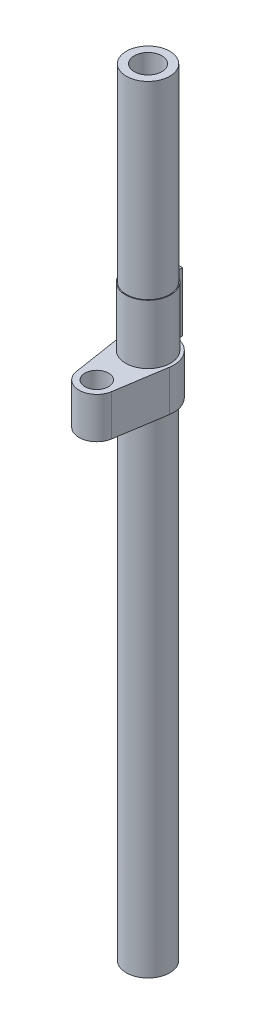
SolidWorks part; units mm, degrees
ref_plane "Ön Düzlem" through (0, 0, 0) normal (0, 0, 1) x (1, 0, 0)
ref_plane "Üst Düzlem" through (0, 0, 0) normal (0, 1, 0) x (1, 0, 0)
ref_plane "Sağ Düzlem" through (0, 0, 0) normal (1, 0, 0) x (0, 0, -1)
sketch "Sketch1" plane through (0, 0, 0) normal (0, 1, 0) x (1, 0, 0)
  circle A0 centre (0, 0) radius 2.75
  dimension "D1" = 5.5
extrude "Boss-Extrude1" add sketch "Sketch1" along normal blind 98.4
sketch "Sketch2" plane through (0, 0, 0) normal (0, -1, 0) x (1, 0, 0)
  circle A0 centre (0, 0) radius 1.75
  dimension "D1" = 3.5
extrude "Cut-Extrude1" cut sketch "Sketch2" against normal blind 10.15
extrude "Cut-Extrude2" cut sketch "Sketch2<2>" along normal blind 10.15 from surface starting at face at (0, 98.4, 2.75)
sketch "Sketch2<2>" plane through (0, 0, 0) normal (0, -1, 0) x (1, 0, 0) same geometry as "Sketch2"
ref_plane "Plane1" through (-2.75, 0, 0) normal (-1, 0, 0) x (0, 0, 1)
sketch "Sketch3" plane through (-2.75, 0, 0) normal (-1, 0, 0) x (0, 0, 1)
  line L0 (0, 7.4) -> (0, 0) construction
  line L1 (2.75, 98.4) -> (-2.75, 98.4) construction
  circle A0 centre (0, 7.4) radius 1.75
  circle A1 centre (0, 91) radius 1.75
  dimension "D2" = 3.5
  dimension "D1" = 7.4
  dimension "D3" = 7.4
extrude "Cut-Extrude3" cut sketch "Sketch3" against normal up to surface (2.75 mm away) up to face at (0, 88.25, 1.75)
ref_plane "Plane2" through (0, 74.45, 0) normal (0, 1, 0) x (1, 0, 0)
sketch "Sketch4" plane through (0, 74.45, 0) normal (0, 1, 0) x (1, 0, 0)
  line L0 (-0.75, 2.9047) -> (-0.75, 3.9047) construction
  line L1 (0.75, 2.9047) -> (0.75, 3.9047) construction
  line L2 (-0.75, 3.4047) -> (0.75, 3.4047) construction
  line L3 (-0.75, 3.9047) -> (0.75, 3.9047) construction
  line L4 (0.6, 2.7861) -> (0.6, 3.7547)
  line L5 (-0.6, 3.7547) -> (0.6, 3.7547)
  line L6 (-0.6, 2.7861) -> (-0.6, 3.7547)
  arc A0 (-0.75, 2.9047) -> (0.75, 2.9047) centre (0, 0) ccw construction
  arc A1 (-0.6, 2.7861) -> (0.6, 2.7861) centre (0, 0) ccw
  circle A2 centre (0, 0) radius 2.75 construction
  circle A3 centre (0, 0) radius 2.75
  point P9 (0, 3.4047)
  dimension "D1" = 6
  dimension "D2" = 1.5
  dimension "D3" = 1
  dimension "D4" = 0.15
extrude "Boss-Extrude2" add sketch "Sketch4" against normal blind 7.5
sketch "Sketch5" plane through (0, 66.95, 0) normal (0, -1, 0) x (1, 0, 0)
  line L0 (-3.2113, 0.5) -> (-2.2232, 6.8462)
  line L1 (2.2232, 6.8462) -> (3.2113, 0.5)
  arc A0 (2.2232, 6.8462) -> (-2.2232, 6.8462) centre (0, 6.5) ccw
  arc A1 (-3.2113, 0.5) -> (3.2113, 0.5) centre (0, 0) ccw
  circle A2 centre (0, 6.5) radius 1.5
  circle A3 centre (0, 0) radius 2.75 construction
  circle A4 centre (0, 0) radius 2.75
  dimension "D1" = 4.5
  dimension "D3" = 6.5
  dimension "D4" = 3
  dimension "D2" = 6.5
extrude "Boss-Extrude3" add sketch "Sketch5" along normal blind 5.2
